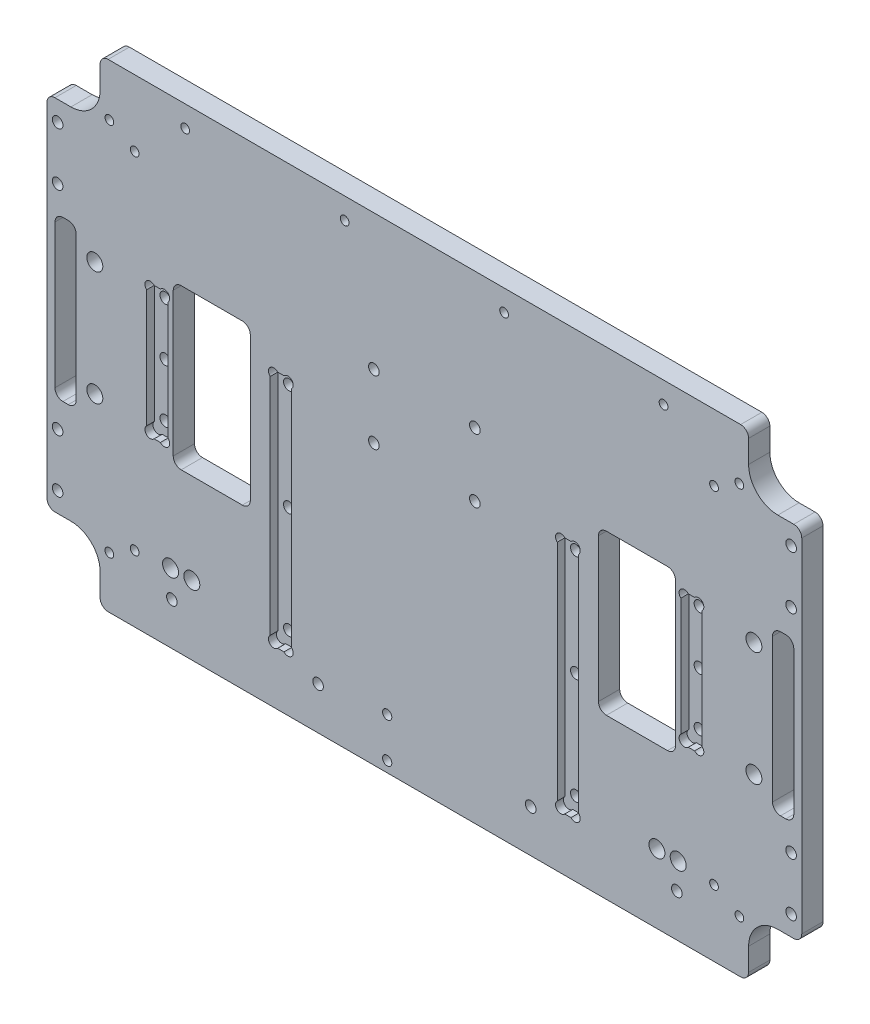
SolidWorks part; units mm, degrees
ref_plane "Front" through (0, 0, 0) normal (0, 0, 1) x (1, 0, 0)
ref_plane "Top" through (0, 0, 0) normal (0, 1, 0) x (1, 0, 0)
ref_plane "Right" through (0, 0, 0) normal (1, 0, 0) x (0, 0, -1)
sketch "Esquisse1" plane through (0, 0, 0) normal (0, 0, 1) x (1, 0, 0)
  line L1 (0, 0) -> (284, 0)
  line L2 (0, 0) -> (0, 180)
  line L3 (0, 180) -> (284, 180)
  line L4 (284, 0) -> (284, 180)
  dimension "D1" = 284
  dimension "D2" = 180
extrude "Boss.-Extru.1" add sketch "Esquisse1" along normal blind 8
sketch "Esquisse2" plane through (0, 0, 8) normal (0, 0, 1) x (1, 0, 0)
  line L0 (142, 180) -> (142, 0) construction
  line L1 (47.5, 60) -> (76.5, 60)
  line L2 (47.5, 60) -> (47.5, 120)
  line L3 (47.5, 120) -> (76.5, 120)
  line L4 (76.5, 60) -> (76.5, 120)
  line L5 (284, 180) -> (0, 180) construction
  line L6 (0, 0) -> (284, 0) construction
  line L7 (76.5, 90) -> (142, 90) construction
  line L8 (62, 60) -> (62, 120) construction
  line L9 (47.5, 90) -> (11, 90) construction
  line L10 (7, 60) -> (7, 120) construction
  line L11 (3, 60) -> (11, 60)
  line L12 (3, 60) -> (3, 120)
  line L13 (3, 120) -> (11, 120)
  line L14 (11, 60) -> (11, 120)
  line L15 (277, 60) -> (277, 120) construction
  line L16 (236.5, 90) -> (273, 90) construction
  line L17 (222, 60) -> (222, 120) construction
  line L18 (273, 60) -> (273, 120)
  line L19 (281, 120) -> (273, 120)
  line L20 (281, 60) -> (281, 120)
  line L21 (281, 60) -> (273, 60)
  line L22 (207.5, 60) -> (207.5, 120)
  line L23 (236.5, 120) -> (207.5, 120)
  line L24 (236.5, 60) -> (236.5, 120)
  line L25 (236.5, 60) -> (207.5, 60)
  dimension "D1" = 90
  dimension "D2" = 60
  dimension "D3" = 29
  dimension "D4" = 160
  dimension "D5" = 8
  dimension "D6" = 60
  dimension "D7" = 270
extrude "Enlèv. mat.-Extru.1" cut sketch "Esquisse2" against normal through all
sketch "Esquisse3" plane through (0, 0, 8) normal (0, 0, 1) x (1, 0, 0)
  line L0 (0, 172) -> (284, 172) construction
  line L1 (0, 180) -> (0, 0) construction
  line L2 (284, 0) -> (284, 180) construction
  line L3 (112, 172) -> (112, 180.3897) construction
  line L5 (172, 172) -> (172, 180.3897) construction
  line L6 (172, 180.3897) -> (112, 180.3897) construction
  line L7 (142, 180.3897) -> (142, 180) construction
  line L8 (284, 180) -> (0, 180) construction
  circle A0 centre (112, 172) radius 1.65
  circle A1 centre (172, 172) radius 1.65
  circle A2 centre (232, 172) radius 1.65
  circle A4 centre (52, 172) radius 1.65
  dimension "D1" = 3.3
  dimension "D2" = 4
  dimension "D3" = 8
  dimension "D4" = 60
extrude "Enlèv. mat.-Extru.2" cut sketch "Esquisse3" against normal up to vertex (8 mm away) up to point (284, 180, 0)
sketch "Esquisse4" plane through (0, 0, 8) normal (0, 0, 1) x (1, 0, 0)
  line L0 (142, 0) -> (142, 180) construction
  line L1 (84, 110) -> (92, 110)
  line L2 (84, 110) -> (84, 20)
  line L3 (84, 20) -> (92, 20)
  line L4 (92, 110) -> (92, 20)
  line L5 (0, 0) -> (284, 0) construction
  line L6 (284, 180) -> (0, 180) construction
  line L8 (76.5, 60) -> (76.5, 120) construction
  line L9 (192, 110) -> (192, 20)
  line L10 (200, 20) -> (192, 20)
  line L11 (200, 110) -> (200, 20)
  line L12 (200, 110) -> (192, 110)
  line L13 (47.5, 120) -> (47.5, 60) construction
  line L14 (37.5, 115) -> (45.5, 115)
  line L15 (37.5, 115) -> (37.5, 65)
  line L16 (37.5, 65) -> (45.5, 65)
  line L17 (45.5, 115) -> (45.5, 65)
  line L18 (45.5, 90) -> (47.5, 90) construction
  line L19 (238.5, 90) -> (236.5, 90) construction
  line L20 (238.5, 115) -> (238.5, 65)
  line L21 (246.5, 65) -> (238.5, 65)
  line L22 (246.5, 115) -> (246.5, 65)
  line L23 (246.5, 115) -> (238.5, 115)
  line L24 (47.5, 60) -> (76.5, 60) construction
  dimension "D1" = 40
  dimension "D2" = 90
  dimension "D3" = 8
  dimension "D4" = 7.5
  dimension "D5" = 8
  dimension "D6" = 2
  dimension "D7" = 50
extrude "Enlèv. mat.-Extru.3" cut sketch "Esquisse4" against normal blind 3
sketch "Esquisse5" plane through (0, 0, 8) normal (0, 0, 1) x (1, 0, 0)
  line L0 (142, 0) -> (142, 124.0722) construction
  line L2 (142, 117) -> (121.1311, 117) construction
  line L3 (0, 180) -> (0, 0) construction
  circle A0 centre (123, 129) radius 2
  circle A1 centre (123, 105) radius 2
  circle A2 centre (161, 105) radius 2
  circle A3 centre (161, 129) radius 2
  circle A5 centre (112, 172) radius 1.65 construction
  dimension "D1" = 38
  dimension "D2" = 4
  dimension "D3" = 24
  dimension "D4" = 55
  dimension "D5" = 142
extrude "Enlèv. mat.-Extru.4" cut sketch "Esquisse5" against normal through all
sketch "Esquisse6" plane through (0, 0, 8) normal (0, 0, 1) x (1, 0, 0)
  line L0 (142, 0) -> (142, 119.0936) construction
  line L1 (0, 0) -> (284, 0) construction
  line L2 (11, 90) -> (29.8915, 90) construction
  line L4 (11, 60) -> (11, 120) construction
  line L5 (273, 90) -> (254.1085, 90) construction
  circle A0 centre (18, 111.5) radius 3
  circle A1 centre (18, 68.5) radius 3
  circle A2 centre (266, 68.5) radius 3
  circle A3 centre (266, 111.5) radius 3
  dimension "D3" = 6
  dimension "D1" = 21.5
  dimension "D2" = 7
extrude "Enlèv. mat.-Extru.5" cut sketch "Esquisse6" against normal through all
sketch "Esquisse8" plane through (0, 0, 8) normal (0, 0, 1) x (1, 0, 0)
  line L0 (142, 180) -> (142, 109.7669) construction
  line L1 (0, 180) -> (20, 180)
  line L2 (0, 180) -> (0, 157.5)
  line L3 (0, 157.5) -> (20, 157.5)
  line L4 (20, 180) -> (20, 157.5)
  line L5 (284, 180) -> (0, 180) construction
  line L6 (264, 180) -> (264, 157.5)
  line L7 (284, 157.5) -> (264, 157.5)
  line L8 (284, 180) -> (284, 157.5)
  line L9 (284, 180) -> (264, 180)
  line L10 (264, 0) -> (264, 22.5)
  line L11 (0, 0) -> (20, 0)
  line L12 (0, 0) -> (0, 22.5)
  line L13 (0, 22.5) -> (20, 22.5)
  line L14 (20, 0) -> (20, 22.5)
  line L15 (284, 22.5) -> (264, 22.5)
  line L16 (284, 0) -> (284, 22.5)
  line L17 (284, 0) -> (264, 0)
  dimension "D1" = 22.5
  dimension "D2" = 20
  dimension "D3" = 22.5
extrude "Enlèv. mat.-Extru.7" cut sketch "Esquisse8" against normal through all
fillet "Congé1" radius 11 4 edges at (20, 157.5, 4) (264, 157.5, 4) (264, 22.5, 4) (20, 22.5, 4)
sketch "Esquisse7" plane through (0, 0, 8) normal (0, 0, 1) x (1, 0, 0)
  line L0 (142, 180) -> (142, 7.3256) construction
  line L1 (264, 180) -> (20, 180) construction
  line L2 (23.4737, 160.5) -> (33, 155) construction
  line L3 (264, 180) -> (20, 180) construction
  line L4 (260.5263, 160.5) -> (251, 155) construction
  line L5 (33, 155) -> (33, 25) construction
  line L6 (33, 90) -> (100.6533, 90) construction
  line L7 (23.4737, 19.5) -> (33, 25) construction
  line L8 (20, 0) -> (264, 0) construction
  line L9 (260.5263, 19.5) -> (251, 25) construction
  circle A0 centre (33, 155) radius 1.65
  circle A1 centre (23.4737, 160.5) radius 1.65
  circle A2 centre (260.5263, 160.5) radius 1.65
  circle A3 centre (251, 155) radius 1.65
  circle A5 centre (23.4737, 19.5) radius 1.65
  circle A6 centre (33, 25) radius 1.65
  circle A7 centre (251, 25) radius 1.65
  circle A8 centre (260.5263, 19.5) radius 1.65
  dimension "D1" = 3.3
  dimension "D5" = 25
  dimension "D2" = 11
  dimension "D3" = 109
  dimension "D4" = 30
  dimension "D6" = 25
extrude "Enlèv. mat.-Extru.6" cut sketch "Esquisse7" against normal through all
fillet "Congé2" radius 3 16 edges at (281, 60, 4) (273, 60, 4) (281, 120, 4) (273, 120, 4) (236.5, 120, 4) (207.5, 120, 4) (236.5, 60, 4) (207.5, 60, 4) (76.5, 60, 4) (47.5, 60, 4) (76.5, 120, 4) (47.5, 120, 4) (11, 120, 4) (3, 120, 4) (3, 60, 4) (11, 60, 4)
sketch "Esquisse9" plane through (0, 0, 8) normal (0, 0, 1) x (1, 0, 0)
  line L0 (37.5, 115) -> (38.8435, 113.6565) construction
  line L1 (45.5, 115) -> (37.5, 115) construction
  line L2 (41.5, 115) -> (41.5, 118.2808) construction
  line L3 (45.5, 115) -> (37.5, 115) construction
  line L4 (45.5, 115) -> (44.1565, 113.6565) construction
  line L5 (45.5, 90) -> (42.8729, 90) construction
  line L6 (45.5, 65) -> (45.5, 115) construction
  line L7 (45.5, 65) -> (44.1565, 66.3435) construction
  line L8 (37.5, 65) -> (38.8435, 66.3435) construction
  line L9 (45.5, 90) -> (238.5, 90) construction
  line L10 (238.5, 115) -> (238.5, 65) construction
  line L11 (142, 90) -> (142, 121.5895) construction
  line L12 (246.5, 65) -> (245.1565, 66.3435) construction
  line L13 (238.5, 65) -> (239.8435, 66.3435) construction
  line L14 (238.5, 90) -> (241.1271, 90) construction
  line L15 (238.5, 115) -> (239.8435, 113.6565) construction
  line L16 (242.5, 115) -> (242.5, 118.2808) construction
  line L17 (246.5, 115) -> (245.1565, 113.6565) construction
  line L18 (84, 110) -> (85.3435, 108.6565) construction
  line L19 (92, 110) -> (84, 110) construction
  line L20 (88, 110) -> (88, 112.2434) construction
  line L21 (92, 110) -> (84, 110) construction
  line L22 (92, 110) -> (90.6565, 108.6565) construction
  line L23 (84, 65) -> (89.3356, 65) construction
  line L24 (84, 110) -> (84, 20) construction
  line L25 (92, 20) -> (90.6565, 21.3435) construction
  line L26 (88, 20) -> (88, 17.7566) construction
  line L27 (84, 20) -> (85.3435, 21.3435) construction
  line L28 (200, 20) -> (198.6565, 21.3435) construction
  line L29 (196, 20) -> (196, 17.7566) construction
  line L30 (192, 20) -> (193.3435, 21.3435) construction
  line L31 (200, 65) -> (194.6644, 65) construction
  line L32 (192, 110) -> (193.3435, 108.6565) construction
  line L33 (196, 110) -> (196, 112.2434) construction
  line L34 (200, 110) -> (198.6565, 108.6565) construction
  circle A0 centre (38.8435, 113.6565) radius 2
  circle A1 centre (44.1565, 113.6565) radius 2
  circle A2 centre (44.1565, 66.3435) radius 2
  circle A3 centre (38.8435, 66.3435) radius 2
  circle A4 centre (245.1565, 66.3435) radius 2
  circle A5 centre (239.8435, 66.3435) radius 2
  circle A6 centre (239.8435, 113.6565) radius 2
  circle A7 centre (245.1565, 113.6565) radius 2
  circle A8 centre (85.3435, 108.6565) radius 2
  circle A9 centre (90.6565, 108.6565) radius 2
  circle A10 centre (90.6565, 21.3435) radius 2
  circle A11 centre (85.3435, 21.3435) radius 2
  circle A12 centre (198.6565, 21.3435) radius 2
  circle A13 centre (193.3435, 21.3435) radius 2
  circle A14 centre (193.3435, 108.6565) radius 2
  circle A15 centre (198.6565, 108.6565) radius 2
  dimension "D1" = 4
  dimension "D6" = 4
  dimension "D2" = 45
  dimension "D3" = 1.9
  dimension "D4" = 45
  dimension "D5" = 1.9
extrude "Enlèv. mat.-Extru.8" cut sketch "Esquisse9" against normal up to vertex (3 mm away) up to point (37.5, 65, 5)
fillet "Congé3" radius 3 8 edges at (264, 180, 4) (284, 157.5, 4) (284, 22.5, 4) (264, 0, 4) (20, 0, 4) (0, 22.5, 4) (0, 157.5, 4) (20, 180, 4)
sketch "Esquisse10" plane through (0, 0, 5) normal (0, 0, 1) x (1, 0, 0)
  line L0 (41.5, 115) -> (41.5, 65) construction
  line L1 (42.6749, 115) -> (40.3251, 115) construction
  line L2 (40.3251, 65) -> (42.6749, 65) construction
  line L3 (41.5, 90) -> (37.5, 90) construction
  line L4 (37.5, 112.1749) -> (37.5, 67.8251) construction
  line L5 (88, 110) -> (88, 20) construction
  line L6 (89.1749, 110) -> (86.8251, 110) construction
  line L7 (86.8251, 20) -> (89.1749, 20) construction
  line L8 (88, 65) -> (84, 65) construction
  line L9 (84, 107.1749) -> (84, 22.8251) construction
  line L10 (142, 0) -> (142, 180) construction
  line L11 (23, 0) -> (261, 0) construction
  line L12 (261, 180) -> (23, 180) construction
  line L13 (196, 65) -> (200, 65) construction
  line L14 (196, 110) -> (196, 20) construction
  line L15 (242.5, 90) -> (246.5, 90) construction
  line L16 (242.5, 115) -> (242.5, 65) construction
  circle A0 centre (41.5, 90) radius 2
  circle A1 centre (41.5, 70) radius 2
  circle A2 centre (41.5, 110) radius 2
  circle A3 centre (88, 65) radius 2
  circle A4 centre (88, 25) radius 2
  circle A5 centre (88, 105) radius 2
  circle A6 centre (196, 105) radius 2
  circle A7 centre (196, 25) radius 2
  circle A8 centre (196, 65) radius 2
  circle A9 centre (242.5, 110) radius 2
  circle A10 centre (242.5, 70) radius 2
  circle A11 centre (242.5, 90) radius 2
  dimension "D1" = 4
  dimension "D2" = 20
  dimension "D3" = 40
extrude "Enlèv. mat.-Extru.9" cut sketch "Esquisse10" against normal through all
sketch "Esquisse11" plane through (0, 0, 8) normal (0, 0, 1) x (1, 0, 0)
  line L0 (142, 0) -> (142, 52.4414) construction
  line L1 (23, 0) -> (261, 0) construction
  line L2 (142, 16) -> (47, 16) construction
  line L3 (86.8251, 20) -> (89.1749, 20) construction
  line L4 (46.5, 26) -> (54.5, 26) construction
  line L5 (237.5, 26) -> (229.5, 26) construction
  circle A0 centre (47, 16) radius 2
  circle A1 centre (237, 16) radius 2
  circle A2 centre (102, 16) radius 2
  circle A3 centre (46.5, 26) radius 3
  circle A4 centre (54.5, 26) radius 3
  circle A5 centre (229.5, 26) radius 3
  circle A6 centre (237.5, 26) radius 3
  circle A7 centre (182, 16) radius 2
  point P10 (94.5, 16)
  point P13 (88, 20)
  dimension "D1" = 4
  dimension "D2" = 190
  dimension "D4" = 8
  dimension "D5" = 10
  dimension "D7" = 6
  dimension "D8" = 80
  dimension "D3" = 4
  dimension "D6" = 87.5
extrude "Enlèv. mat.-Extru.10" cut sketch "Esquisse11" against normal through all
sketch "Esquisse12" plane through (0, 0, 8) normal (0, 0, 1) x (1, 0, 0)
  line L0 (128, 0) -> (128, 19) construction
  line L1 (23, 0) -> (261, 0) construction
  circle A0 centre (128, 4) radius 1.75
  circle A1 centre (128, 19) radius 1.75
  dimension "D1" = 15
  dimension "D2" = 3.5
  dimension "D3" = 4
  dimension "D4" = 128
extrude "Enlèv. mat.-Extru.11" cut sketch "Esquisse12" against normal through all
sketch "Esquisse13" plane through (0, 0, 8) normal (0, 0, 1) x (1, 0, 0)
  line L0 (4, 157.5) -> (4, 22.5) construction
  line L1 (3, 157.5) -> (9, 157.5) construction
  line L2 (9, 22.5) -> (3, 22.5) construction
  line L3 (0, 154.5) -> (0, 25.5) construction
  line L4 (11, 90) -> (4, 90) construction
  line L5 (11, 63) -> (11, 117) construction
  line L6 (142, 0) -> (142, 180) construction
  line L7 (23, 0) -> (261, 0) construction
  line L8 (261, 180) -> (23, 180) construction
  line L9 (273, 90) -> (280, 90) construction
  line L10 (280, 157.5) -> (280, 22.5) construction
  circle A0 centre (4, 30) radius 2
  circle A1 centre (4, 50) radius 2
  circle A2 centre (4, 130) radius 2
  circle A3 centre (4, 150) radius 2
  circle A4 centre (280, 150) radius 2
  circle A5 centre (280, 130) radius 2
  circle A6 centre (280, 50) radius 2
  circle A7 centre (280, 30) radius 2
  dimension "D2" = 20
  dimension "D3" = 4
  dimension "D4" = 80
  dimension "D1" = 4
extrude "Enlèv. mat.-Extru.12" cut sketch "Esquisse13" against normal through all
